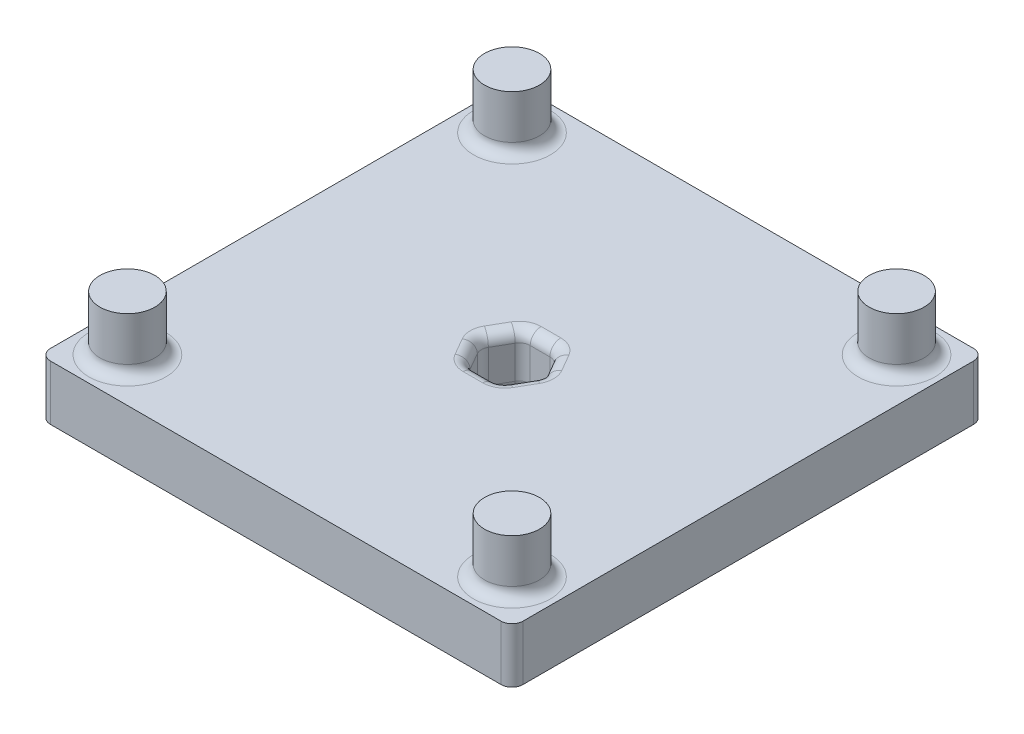
SolidWorks part; units mm, degrees
ref_plane "Front Plane" through (0, 0, 0) normal (0, 0, 1) x (1, 0, 0)
ref_plane "Top Plane" through (0, 0, 0) normal (0, 1, 0) x (1, 0, 0)
ref_plane "Right Plane" through (0, 0, 0) normal (1, 0, 0) x (0, 0, -1)
sketch "Sketch2" plane through (0, 0, 0) normal (0, 1, 0) x (1, 0, 0)
  line L4 (-21.5, -21.5) -> (21.5, -21.5)
  line L9 (2.9445, 0) -> (1.4722, 2.55)
  line L10 (1.4722, 2.55) -> (-1.4722, 2.55)
  line L11 (-1.4722, 2.55) -> (-2.9445, 0)
  line L12 (-2.9445, 0) -> (-1.4722, -2.55)
  line L13 (-1.4722, -2.55) -> (1.4722, -2.55)
  line L14 (1.4722, -2.55) -> (2.9445, 0)
  line L15 (21.5, -21.5) -> (21.5, 21.5)
  line L16 (21.5, 21.5) -> (-21.5, 21.5)
  line L17 (-21.5, 21.5) -> (-21.5, -21.5)
  line L18 (0, 0) -> (21.5, 0)
  line L19 (0, 0) -> (-21.5, 0)
  circle A0 centre (0, 0) radius 2.55 construction
  circle A4 centre (17.5, -17.5) radius 4
  circle A5 centre (17.5, -17.5) radius 2.5
  circle A6 centre (17.5, 17.5) radius 4
  circle A7 centre (17.5, 17.5) radius 2.5
  circle A8 centre (-17.5, 17.5) radius 4
  circle A9 centre (-17.5, 17.5) radius 2.5
  circle A10 centre (-17.5, -17.5) radius 4
  circle A11 centre (-17.5, -17.5) radius 2.5
  dimension "D1" = 5.1
  dimension "D3" = 8
  dimension "D4" = 1.5
  dimension "D2" = 43
extrude "Boss-Extrude1" add sketch "Sketch2" along normal blind 5 contours A8 A9 | A8 L16 L17 | A8 L17 L19 L11 L10 L9 L18 L15 A6 L16 | A6 A7 | A6 L15 L16 | A10 L4 A4 L15 L18 L14 L13 L12 L19 L17 | A4 A5 | A4 L4 L15 | A10 L17 L4 | A10 A11 | A11 | A9 | A7 | A5 region at (-20.6065, 0, 20.6065) region at (0, 0, 9.9583) region at (-20.2484, 0, 20.2484) region at (20.6065, 0, 20.6065) region at (14.7516, 0, 14.7516) region at (0, 0, -9.9583) region at (-20.6065, 0, -20.6065) region at (-20.2484, 0, -20.2484) region at (20.6065, 0, -20.6065) region at (14.7516, 0, -14.7516) region at (17.5, 0, 17.5) region at (17.5, 0, -17.5) region at (-17.5, 0, -17.5) region at (-17.5, 0, 17.5)
extrude "Boss-Extrude2" add sketch "Sketch2<3>" along normal blind 10 contours A9 | A7 | A5 | A11 region at (17.5, 0, 17.5) region at (17.5, 0, -17.5) region at (-17.5, 0, -17.5) region at (-17.5, 0, 17.5)
sketch "Sketch2<3>" plane through (0, 0, 0) normal (0, 1, 0) x (1, 0, 0) same geometry as "Sketch2"
fillet "Fillet1" radius 1 4 edges at (-17.5, 5, -15) (17.5, 5, -15) (17.5, 5, 20) (-17.5, 5, 20)
fillet "Fillet2" radius 1 10 edges at (-1.4722, 2.5, -2.55) (1.4722, 2.5, -2.55) (2.9445, 2.5, 0) (1.4722, 2.5, 2.55) (-1.4722, 2.5, 2.55) (-2.9445, 2.5, 0) (-21.5, 2.5, -21.5) (21.5, 2.5, -21.5) (21.5, 2.5, 21.5) (-21.5, 2.5, 21.5)
fillet "Fillet3" radius 1 24 edges at (1.3949, 0, 2.416) (0, 0, 2.55) (-1.3949, 0, 2.416) (-2.2084, 0, 1.275) (-2.7898, 5, 0) (-2.7898, 0, 0) (-1.3949, 5, 2.416) (1.3949, 5, 2.416) (2.7898, 5, 0) (2.7898, 0, 0) (1.3949, 5, -2.416) (1.3949, 0, -2.416) (-1.3949, 5, -2.416) (-1.3949, 0, -2.416) (0, 5, 2.55) (2.2084, 5, 1.275) (2.2084, 5, -1.275) (0, 5, -2.55) (-2.2084, 5, -1.275) (-2.2084, 5, 1.275) (2.2084, 0, 1.275) (2.2084, 0, -1.275) (0, 0, -2.55) (-2.2084, 0, -1.275)
